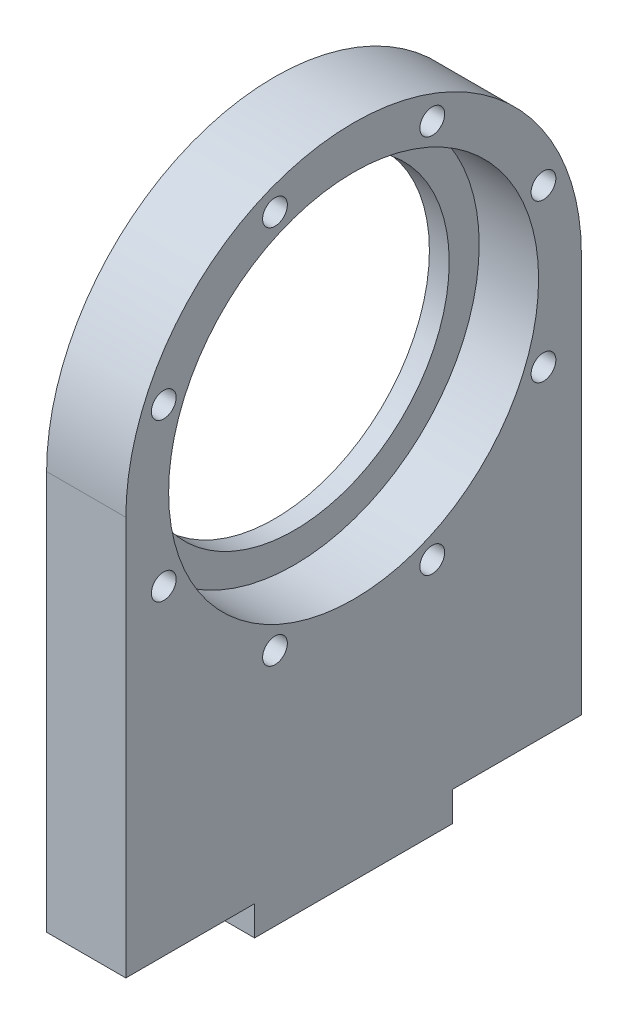
SolidWorks part; units mm, degrees
material "3d打印 35%"
ref_plane "前视基准面" through (0, 0, 0) normal (0, 0, 1) x (1, 0, 0)
ref_plane "上视基准面" through (0, 0, 0) normal (0, 1, 0) x (1, 0, 0)
ref_plane "右视基准面" through (0, 0, 0) normal (1, 0, 0) x (0, 0, -1)
other "Configuration Table"
sketch "草图1" plane through (0, 0, 0) normal (1, 0, 0) x (0, 0, -1)
  line L0 (0, 0) -> (0, 43.0868) construction
  line L1 (0, 0) -> (13.8083, 33.3362) construction
  circle A0 centre (0, 0) radius 23
  circle A1 centre (0, 0) radius 21.6522 construction
  circle A2 centre (0, 0) radius 15.6522
  circle A3 centre (0, 0) radius 18.68
  circle A4 centre (7.9407, 19.1705) radius 1.25
  circle A5 centre (19.1705, 7.9407) radius 1.25
  circle A6 centre (19.1705, -7.9407) radius 1.25
  circle A7 centre (7.9407, -19.1705) radius 1.25
  circle A8 centre (-7.9407, -19.1705) radius 1.25
  circle A9 centre (-19.1705, -7.9407) radius 1.25
  circle A10 centre (-19.1705, 7.9407) radius 1.25
  circle A11 centre (-7.9407, 19.1705) radius 1.25
  point P27 (0, 0)
  dimension "D1" = 8
  dimension "D2" = 46
  dimension "D3" = 2.5
  dimension "D4" = 2.5
  dimension "D5" = 2.5
  dimension "D6" = 20.75
  dimension "D7" = 37.36
  dimension "D8" = 46
extrude "凸台-拉伸2" add sketch "草图1" along normal blind 2 contours A3 A2 region at (0, 0, 18.1516)
extrude "凸台-拉伸3" add sketch "草图1<4>" along normal blind 8 contours A0 A11 A10 A9 A8 A7 A6 A5 A4 A3 region at (0, 0, 22.3495)
sketch "草图1<4>" plane through (0, 0, 0) normal (1, 0, 0) x (0, 0, -1) same geometry as "草图1"
sketch "草图2" plane through (0, 0, 0) normal (-1, 0, 0) x (0, 0, 1)
  line L0 (0, -200000) -> (0, 200043.0868) construction
  line L2 (-23, -40.29) -> (-23, 0)
  line L4 (23, -40.29) -> (23, 0)
  line L5 (-23, -46) -> (23, 0) construction
  line L6 (-23, 0) -> (23, -46) construction
  line L7 (-23, -40.29) -> (23, -40.29)
  circle A0 centre (0, 0) radius 23 construction
  arc A1 (-23, 0) -> (23, 0) centre (0, 0) ccw
  point P0 (0, -23)
extrude "凸台-拉伸4" add sketch "草图2" against normal blind 8
ref_plane "基准面1" through (4, 0, 0) normal (1, 0, 0) x (0, 0, -1)
ref_axis "基准轴1" through (4, -40.29, -23) along (0, 0, 1)
sketch "草图3" plane through (0, -40.29, 0) normal (0, -1, 0) x (1, 0, 0)
  line L0 (4, -25.3) -> (4, 25.3) construction
  line L1 (8, 23) -> (0, 23) construction
  circle A0 centre (4, 19) radius 1.8
  dimension "D1" = 4
extrude "切除-拉伸1" cut sketch "草图3" against normal blind 5
ref_plane "基准面2" through (0, 0, 0) normal (0, 0, -1) x (-1, 0, 0)
mirror "镜向1" about plane through (0, 0, 0) normal (0, 0, -1) of "切除-拉伸1"
ref_point "点2"
sketch "草图4" plane through (0, -40.29, 0) normal (0, -1, 0) x (-1, 0, 0)
  line L0 (-8, 23) -> (-8, -23) construction
  line L1 (0, -10) -> (-8, -10)
  line L2 (0, -10) -> (0, 10)
  line L3 (0, 10) -> (-8, 10)
  line L4 (-8, -10) -> (-8, 10)
  line L5 (0, -10) -> (-8, 10) construction
  line L6 (0, 10) -> (-8, -10) construction
  point P0 (-4, 0)
extrude "凸台-拉伸5" add sketch "草图4" along normal blind 3
